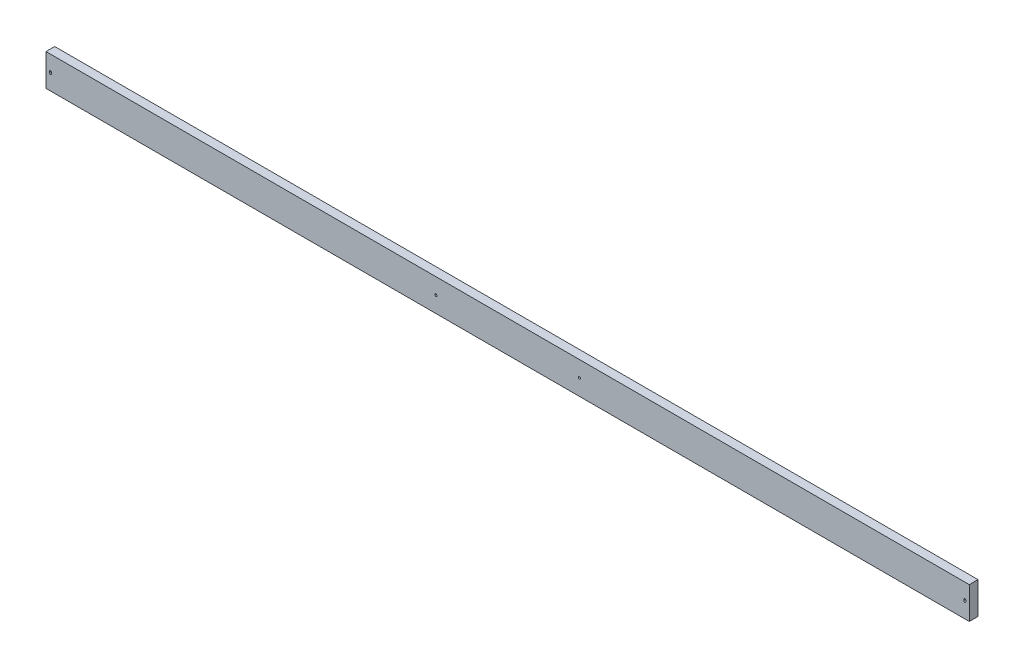
SolidWorks part; units mm, degrees
ref_plane "Front Plane" through (0, 0, 0) normal (0, 0, 1) x (1, 0, 0)
ref_plane "Top Plane" through (0, 0, 0) normal (0, 1, 0) x (1, 0, 0)
ref_plane "Right Plane" through (0, 0, 0) normal (1, 0, 0) x (0, 0, -1)
sketch "Sketch1" plane through (0, 0, 0) normal (0, 0, 1) x (1, 0, 0)
  line L1 (0, 0) -> (4038.6, 0)
  line L2 (0, 0) -> (0, -139.7)
  line L3 (0, -139.7) -> (4038.6, -139.7)
  line L4 (4038.6, 0) -> (4038.6, -139.7)
  dimension "D1" = 4038.6
  dimension "D2" = 139.7
extrude "Boss-Extrude1" add sketch "Sketch1" along normal blind 38.1
sketch "Sketch2" plane through (0, 0, 38.1) normal (0, 0, 1) x (1, 0, 0)
  line L0 (24.0114, -67.4433) -> (24.0114, -72.4471)
  line L1 (4038.6, 0) -> (0, 0) construction
  line L2 (15.0114, -67.3481) -> (15.0114, -72.3519)
  line L3 (0, 0) -> (0, -139.7) construction
  line L5 (4023.5886, -67.3481) -> (4023.5886, -72.3519)
  line L6 (4014.5886, -67.2529) -> (4014.5886, -72.2567)
  line L7 (4038.6, -139.7) -> (4038.6, 0) construction
  arc A0 (24.0114, -67.4433) -> (15.0114, -67.3481) centre (19.5109, -67.4433) ccw
  arc A1 (24.0114, -72.4471) -> (15.0114, -72.3519) centre (19.5109, -72.4471) cw
  arc A2 (4023.5886, -67.3481) -> (4014.5886, -67.2529) centre (4019.0881, -67.3481) ccw
  arc A3 (4023.5886, -72.3519) -> (4014.5886, -72.2567) centre (4019.0881, -72.3519) cw
  point P8 (15.0114, -69.85)
  point P18 (4023.5886, -69.85)
  dimension "D3" = 4.5005
  dimension "D5" = 4.5005
  dimension "D1" = 5.0038
  dimension "D2" = 9
  dimension "D4" = 15.0114
  dimension "D6" = 69.85
  dimension "D7" = 15.0114
  dimension "D8" = 69.85
extrude "Cut-Extrude1" cut sketch "Sketch2" against normal through all
sketch "Sketch3" plane through (0, 0, 38.1) normal (0, 0, 1) x (1, 0, 0)
  line L0 (2019.3, 0) -> (2019.3, -139.7) construction
  line L1 (4038.6, 0) -> (0, 0) construction
  line L2 (0, -139.7) -> (4038.6, -139.7) construction
  circle A0 centre (2333.1678, -69.85) radius 4.7625
  circle A1 centre (1705.4322, -69.85) radius 4.7625
  point P10 (2019.3, -69.85)
  dimension "D1" = 9.525
  dimension "D2" = 9.525
  dimension "D3" = 313.8678
  dimension "D4" = 313.8678
extrude "Cut-Extrude2" cut sketch "Sketch3" against normal through all
